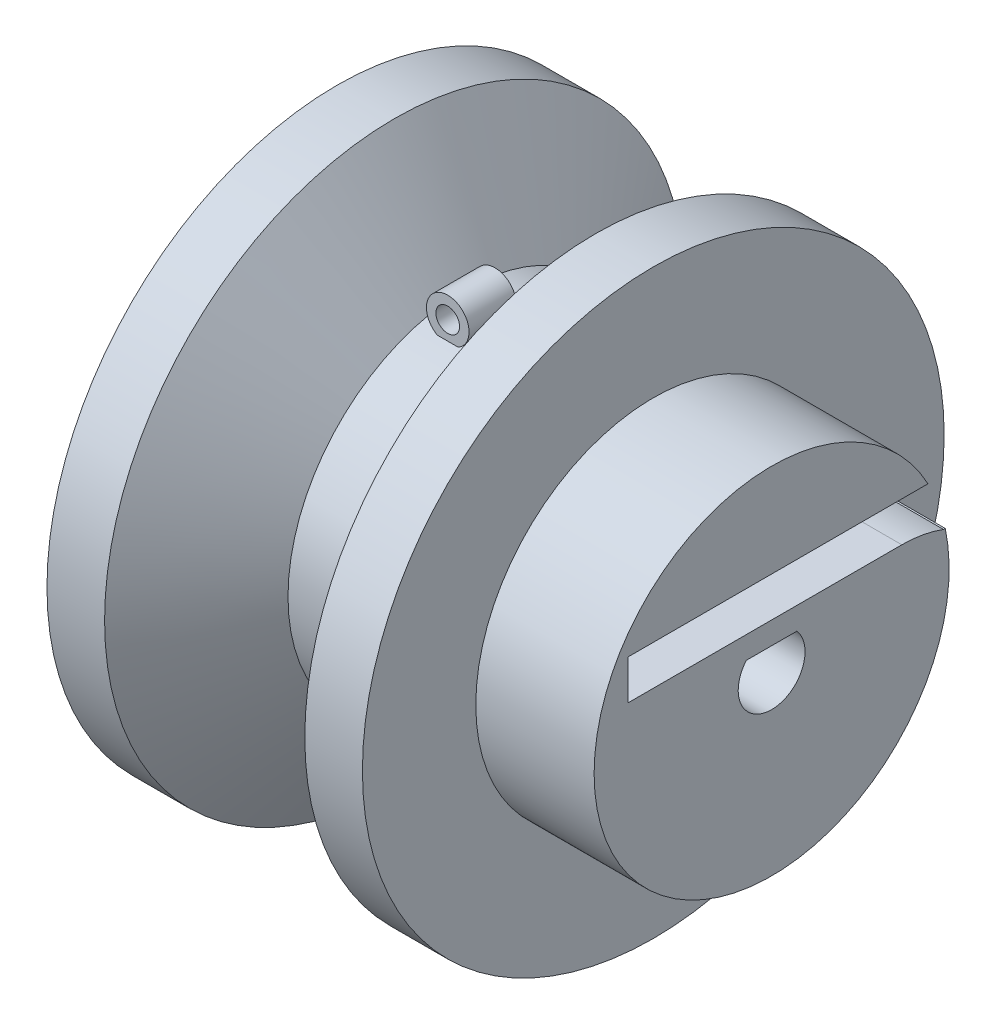
SolidWorks part; units mm, degrees
ref_plane "前基準面" through (0, 0, 0) normal (0, 0, 1) x (1, 0, 0)
ref_plane "上基準面" through (0, 0, 0) normal (0, 1, 0) x (1, 0, 0)
ref_plane "右基準面" through (0, 0, 0) normal (1, 0, 0) x (0, 0, -1)
sketch "草圖1" plane through (0, 0, 0) normal (0, 0, 1) x (1, 0, 0)
  line L0 (0, 0) -> (0, 24.5)
  line L1 (0, 24.5) -> (4.87, 24.5)
  line L2 (4.87, 24.5) -> (10.87, 15)
  line L3 (10.87, 15) -> (15.87, 15)
  line L4 (15.87, 15) -> (21.87, 24.5811)
  line L5 (21.87, 24.5811) -> (26.74, 24.5811)
  line L6 (26.74, 24.5811) -> (26.74, 15)
  line L7 (26.74, 15) -> (36.74, 15)
  line L8 (36.74, 15) -> (36.74, 0)
  line L9 (-743.1564, 0) -> (36475.4845, 0) construction
  line L10 (0, 0) -> (36.74, 0)
  dimension "D1" = 24.5
  dimension "D2" = 4.87
  dimension "D3" = 6
  dimension "D4" = 5
  dimension "D5" = 6
  dimension "D6" = 4.87
  dimension "D7" = 10
  dimension "D8" = 15
revolve "旋轉1" add sketch "草圖1" angle 360 about L9
ref_plane "平面1" through (0, 12, 0) normal (0, 1, 0) x (1, 0, 0)
sketch "草圖3" plane through (36.74, 0, 0) normal (1, 0, 0) x (0, 0, -1)
  circle A0 centre (0, 0) radius 2.825
  dimension "D1" = 5.65
extrude "除料-伸長2" cut sketch "草圖3" against normal blind 35
ref_plane "平面2" through (0, 22, 0) normal (0, 1, 0) x (1, 0, 0)
sketch "草圖16" plane through (36.74, 0, 0) normal (1, 0, 0) x (0, 0, -1)
  line L1 (-2.61, 2.851) -> (2.3989, 2.851)
  line L2 (-2.61, 2.851) -> (-2.61, 1.851)
  line L3 (-2.61, 1.851) -> (2.3989, 1.851)
  line L4 (2.3989, 2.851) -> (2.3989, 1.851)
  dimension "D1" = 1
extrude "填料-伸長2" add sketch "草圖16" against normal blind 30
sketch "草圖19" plane through (36.74, 0, 0) normal (1, 0, 0) x (0, 0, -1)
  line L1 (-0.5637, 2.9297) -> (0.3954, 2.9297)
  line L2 (-0.5637, 2.9297) -> (-0.5637, 2.4182)
  line L3 (-0.5637, 2.4182) -> (0.3954, 2.4182)
  line L4 (0.3954, 2.9297) -> (0.3954, 2.4182)
extrude "填料-伸長3" add sketch "草圖19" against normal blind 30
sketch "草圖24" plane through (36.74, 0, 0) normal (1, 0, 0) x (0, 0, -1)
  line L1 (-12.1511, 7.0982) -> (14.6765, 7.0982)
  line L2 (-12.1511, 7.0982) -> (-12.1511, 3.0982)
  line L3 (-12.1511, 3.0982) -> (14.6765, 3.0982)
  line L4 (14.6765, 7.0982) -> (14.6765, 3.0982)
  line L5 (-12.1511, 7.0982) -> (14.6765, 3.0982) construction
  line L6 (-12.1511, 3.0982) -> (14.6765, 7.0982) construction
  circle A0 centre (0, 0) radius 15 construction
  point P0 (1.2627, 5.0982)
  dimension "D1" = 4
extrude "除料-伸長8" cut sketch "草圖24" against normal blind 9
ref_plane "平面3" through (0, 0, 2) normal (0, 0, 1) x (1, 0, 0)
sketch "草圖26" plane through (0, 0, 2) normal (0, 0, 1) x (1, 0, 0)
  line L0 (13.37, -985) -> (13.37, 49015) construction
  line L1 (15.87, 15) -> (10.87, 15) construction
  circle A0 centre (13.37, 16.0238) radius 1
  point P5 (13.37, 15)
  dimension "D1" = 2
extrude "伸長-薄件1" add sketch "草圖26" along normal blind 2 and the other way blind 2 thin thin type one direction wall 0.8
sketch "草圖27" plane through (0, 12, 0) normal (0, 1, 0) x (1, 0, 0)
  line L0 (-963.26, 0) -> (49036.74, 0) construction
  line L1 (36.74, -15) -> (36.74, 15) construction
  line L2 (31.74, -1015) -> (31.74, 48985) construction
  line L3 (26.74, -15) -> (36.74, -15) construction
  line L4 (23.066, -956.4258) -> (23.066, 49043.5742) construction
  circle A0 centre (31.5457, 0) radius 1.43
  point P5 (36.74, 0)
  point P10 (31.74, -15)
  dimension "D1" = 2.86
extrude "除料-伸長9" cut sketch "草圖27" against normal blind 7
sketch "草圖28" plane through (27.74, 0, 0) normal (1, 0, 0) x (0, 0, -1)
  line L1 (-12.1511, 3.0982) -> (14.5266, 3.0982)
  line L2 (-12.1511, 3.0982) -> (-12.1511, 3.7388)
  line L3 (-12.1511, 3.7388) -> (14.5266, 3.7388)
  line L4 (14.5266, 3.0982) -> (14.5266, 3.7388)
  circle A0 centre (0, 0) radius 15 construction
extrude "填料-伸長4" add sketch "草圖28" along normal blind 9
fillet "圓角1" radius 10 1 edges at (32.24, 3.7388, -14.5266)
